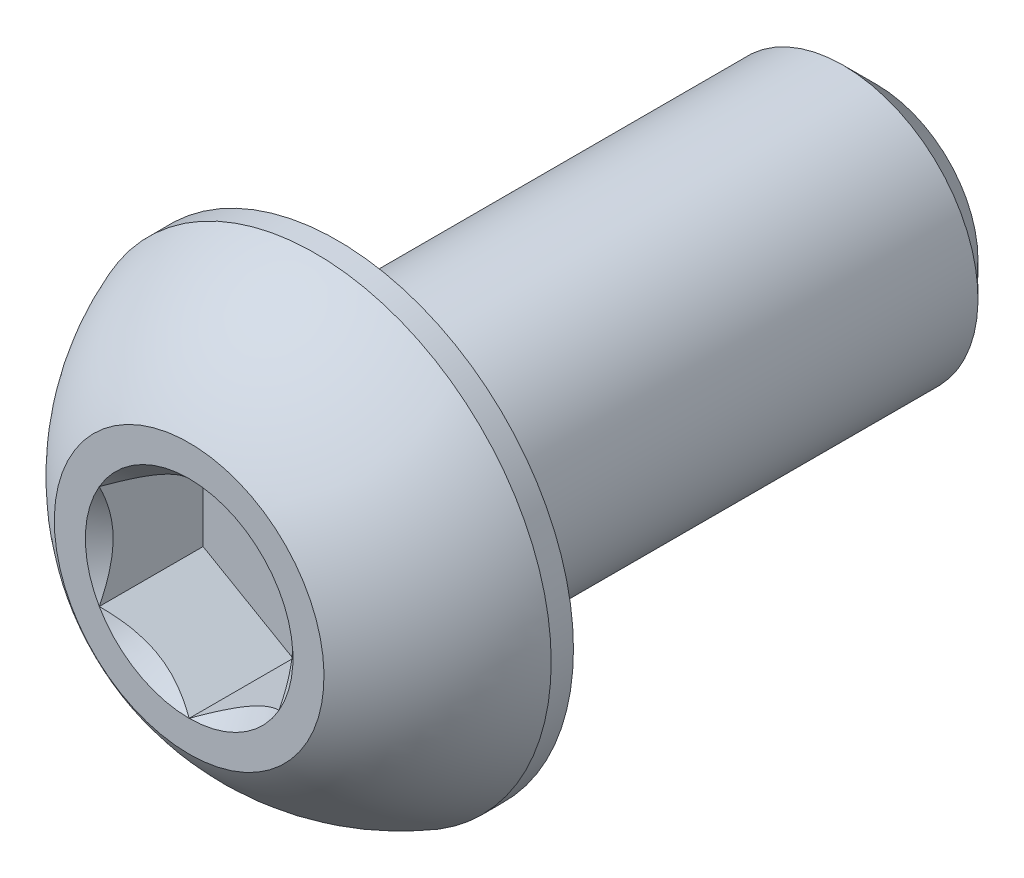
SolidWorks part; units mm, degrees
material "AISI 304"
ref_plane "Front" through (0, 0, 0) normal (0, 0, 1) x (1, 0, 0)
ref_plane "Top" through (0, 0, 0) normal (0, 1, 0) x (1, 0, 0)
ref_plane "Right" through (0, 0, 0) normal (1, 0, 0) x (0, 0, -1)
sketch "Sketch1" plane through (0, 0, 0) normal (1, 0, 0) x (0, 0, -1)
  line L2 (3.3, 3) -> (15.3, 3)
  line L3 (15.3, 3) -> (15.3, 0)
  line L4 (15.3, 0) -> (3.3, 0)
  line L6 (2.805, 5.25) -> (3.3, 5.25) construction
  line L7 (15.3, 3) -> (15.3, -3) construction
  line L8 (0, 0) -> (3.3, 0) construction
  line L9 (3.3, 5.25) -> (3.3, -5.25) construction
  line L11 (3.3, 3) -> (3.3, 0)
  line L13 (0, 2) -> (0, -2) construction
  line L14 (0, 2) -> (0, 3) construction
  arc A3 (0, 3) -> (2.805, 5.25) centre (4.7113, 0) cw construction
  dimension "D1" = 0.495
revolve "Revolve1" add sketch "Sketch1" angle 360 mid plane about L4
sketch "Sketch3" plane through (0, 0, -15.3) normal (0, 0, -1) x (-1, 0, 0)
  circle A0 centre (0, 0) radius 3
curve "Helix/Spiral1" pitch 1 height 13 turns 13
chamfer "Chamfer1" distance 0.75 angle 45 1 edges at (0, 3, -15.3)
sketch "Sketch7" plane through (0, 0, 0) normal (1, 0, 0) x (0, 0, -1)
  line L6 (2.805, 5.25) -> (3.3, 5.25) construction
  line L8 (0, 0) -> (3.3, 0) construction
  line L11 (3.3, 5.25) -> (3.3, -5.25) construction
  line L12 (2.805, 5.25) -> (3.3, 5.25)
  line L13 (0, 0) -> (3.3, 0)
  line L14 (0, 2) -> (0, -2) construction
  line L15 (3.3, 5.25) -> (3.3, 0)
  line L16 (0, 3) -> (0, 0)
  arc A2 (2.805, 5.25) -> (0, 3) centre (4.7113, 0) ccw construction
  arc A3 (2.805, 5.25) -> (0, 3) centre (4.7113, 0) ccw
revolve "Revolve2" add sketch "Sketch7" angle 360 mid plane about L13
sketch "Sketch5" plane through (0, 0, 0) normal (0, 0, 1) x (1, 0, 0)
  line L1 (2, -1.1547) -> (2, 1.1547)
  line L2 (2, 1.1547) -> (0, 2.3094)
  line L3 (0, 2.3094) -> (-2, 1.1547)
  line L4 (-2, 1.1547) -> (-2, -1.1547)
  line L5 (-2, -1.1547) -> (0, -2.3094)
  line L6 (0, -2.3094) -> (2, -1.1547)
  circle A0 centre (0, 0) radius 2 construction
extrude "Cut-Extrude2" cut sketch "Sketch5" against normal blind 2.31
sketch "Sketch6" plane through (0, 0, 0) normal (0, 0, 1) x (1, 0, 0)
  circle A0 centre (0, 0) radius 2.3094
extrude "Cut-Extrude3" cut sketch "Sketch6" against normal blind 2.31 draft 45
sketch "Sketch2" plane through (0, 0, 0) normal (1, 0, 0) x (0, 0, -1)
  line L0 (14.55, 3) -> (15.425, 3)
  line L1 (15.425, 3) -> (15.05, 2.3505)
  line L2 (15.05, 2.3505) -> (14.925, 2.3505)
  line L3 (14.925, 2.3505) -> (14.55, 3)
  line L4 (14.7375, 2.6752) -> (15.2375, 2.6752) construction
  dimension "D1" = 60
  dimension "D2" = 0.125
  dimension "D3" = 0.5
sweep "Cut-Sweep1" [suppressed] cut profiles "Sketch2" path "Helix/Spiral1"
sketch "Sketch10" plane through (0, 0, 0) normal (1, 0, 0) x (0, 0, -1)
  line L0 (15.3, 3) -> (15.3, -3) construction
  point P0 (13.8, -3)
  dimension "D1" = 1.5
ref_axis "Center Axis 1" through (0, 0, -8.1113) along (0, 0, 1)
ref_plane "Contact Plane 1" through (0, 0, -3.3) normal (0, 0, -1) x (-1, 0, 0)
ref_plane "Contact Plane 2" through (0, 0, 0) normal (0, 0, 1) x (1, 0, 0)
equation "\"D3@Helix/Spiral1\" = \"Lg@Sketch1\" + \"D4@Helix/Spiral1\""
equation "\"D2@Sketch2\" = \"D4@Helix/Spiral1\" * .125"
equation "\"D3@Sketch2\" = \"D4@Helix/Spiral1\" * .5"
equation "\"D1@Chamfer1\" = \"D4@Helix/Spiral1\" * .75"
equation "\"D1@Cut-Extrude2\" = \"Head Ht@Sketch1\" * .7"
equation "\"D1@Sketch1\" = \"Head Ht@Sketch1\" * .15"
equation "\"D1@Sketch10\" = \"D4@Helix/Spiral1\" * 1.5"
equation "\"D1@Cut-Extrude3\" = \"D1@Cut-Extrude2\""
